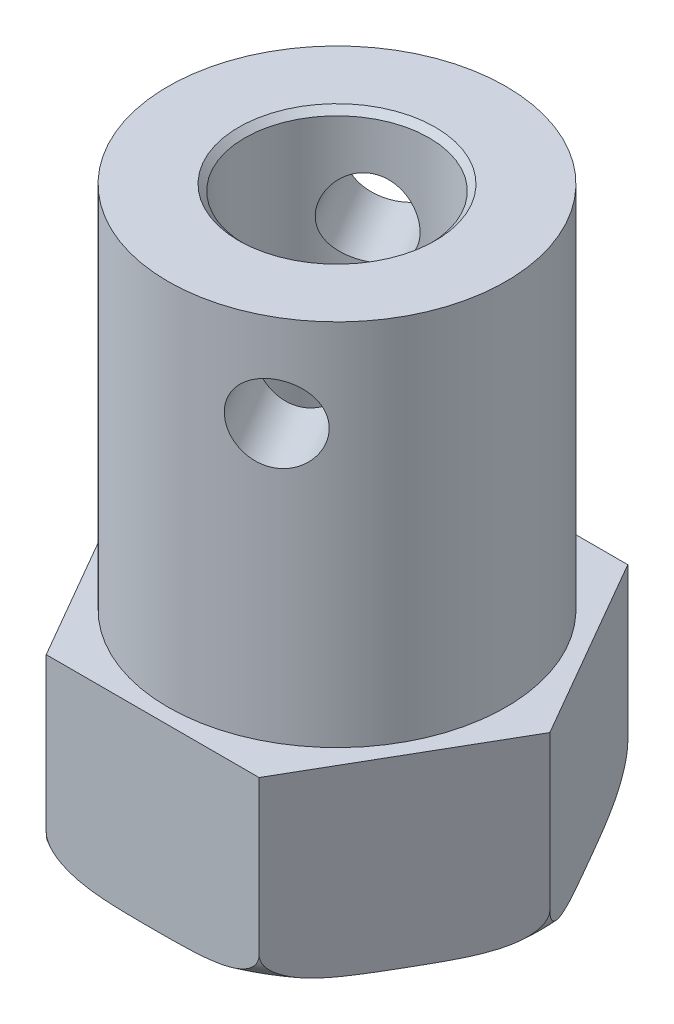
SolidWorks part; units mm, degrees
material "Acero inoxidable al cromo"
ref_plane "Front Plane" through (0, 0, 0) normal (0, 0, 1) x (1, 0, 0)
ref_plane "Top Plane" through (0, 0, 0) normal (0, 1, 0) x (1, 0, 0)
ref_plane "Right Plane" through (0, 0, 0) normal (1, 0, 0) x (0, 0, -1)
sketch "Sketch1" plane through (0, 0, 0) normal (0, 1, 0) x (1, 0, 0)
  line L1 (3.4641, -6) -> (6.9282, 0)
  line L2 (6.9282, 0) -> (3.4641, 6)
  line L3 (3.4641, 6) -> (-3.4641, 6)
  line L4 (-3.4641, 6) -> (-6.9282, 0)
  line L5 (-6.9282, 0) -> (-3.4641, -6)
  line L6 (-3.4641, -6) -> (3.4641, -6)
  circle A0 centre (0, 0) radius 6 construction
  dimension "D1" = 12
extrude "BASE" add sketch "Sketch1" along normal blind 6
sketch "Sketch2" plane through (0, 6, 0) normal (0, 1, 0) x (1, 0, 0)
  line L1 (0, 5.5) -> (0, 6) construction
  line L2 (3.4641, 6) -> (-3.4641, 6) construction
  circle A0 centre (0, 0) radius 5.5
  dimension "D1" = 0.5
  dimension "D2" = 11
extrude "SHAFT HOLDING BODY" add sketch "Sketch2" along normal blind 12
hole_wizard "M4x0.7 Tapped Hole1" positions "Sketch3" profile "Sketch4" tap size "M4x0.7" standard "ANSI Metric" end condition through all
sketch "Sketch3" plane through (0, 0, 0) normal (0, -1, 0) x (-1, 0, 0)
  point P0 (0, 0)
sketch "Sketch4" plane through (0, 0, 0) normal (1, 0, 0) x (0, 0, -1)
  line L0 (0, 0) -> (0, 18)
  line L1 (0, 18) -> (1.65, 18)
  line L2 (1.65, 18) -> (1.65, 0.35)
  line L3 (1.65, 0.35) -> (2, 0)
  line L5 (2, 0) -> (0, 0)
  line L6 (-1.65, 0.35) -> (-2, 0) construction
  line L11 (0, -6.35) -> (0, 107.95) construction
  dimension "Thru Tap Drill Dia." = 3.3
  dimension "Thru Tap Drill Depth" = 18
  dimension "Near C'Sink Dia." = 4
  dimension "Near C'Sink Angle" = 90
cosmetic thread "Hole Thread3" parameters "D2"=4
ref_plane "SET SCREW REFERENCE PLANE" through (2.75, 6, 4.7631) normal (0.5, 0, 0.866) x (0.866, 0, -0.5)
hole_wizard "M3x0.5 Tapped Hole1" positions "Sketch7" profile "Sketch8" tap size "M3x0.5" standard "ANSI Metric" end condition through all
sketch "Sketch7" plane through (2.75, 6, 4.7631) normal (0.5, 0, 0.866) x (0.866, 0, -0.5)
  line L0 (5.5, 12) -> (-5.5, 12) construction
  line L1 (0, 12) -> (0, 0) construction
  line L2 (0, 12) -> (0, 9) construction
  point P0 (0, 9)
  dimension "D1" = 3
sketch "Sketch8" plane through (2.75, 15, 4.7631) normal (0, 1, 0) x (0.866, 0, -0.5)
  line L0 (0, 0) -> (0, 14.1603)
  line L1 (0, 14.1603) -> (1.25, 14.1603)
  line L2 (1.25, 14.1603) -> (1.25, 0)
  line L5 (1.25, 0) -> (0, 0)
  line L11 (0, -6.35) -> (0, 107.95) construction
  dimension "Thru Tap Drill Dia." = 2.5
  dimension "Thru Tap Drill Depth" = 14.1603
cosmetic thread "Hole Thread2" parameters "D2"=3
sketch "Sketch9" plane through (0, 0, 0) normal (0, 0, 1) x (1, 0, 0)
  line L0 (-6.9282, 1) -> (-6.9282, 0)
  line L1 (-6.9282, 0) -> (-5.9282, 0)
  line L2 (6, 0) -> (-6, 0) construction
  line L4 (-6.9282, 6) -> (-6.9282, 0) construction
  arc A0 (-6.9282, 1) -> (-5.9282, 0) centre (-5.9282, 1) ccw
  dimension "D1" = 1
revolve "BASE CHAMFER RELIEF" cut sketch "Sketch9" angle 360 about axis through (0, 0, 0) along (0, 1, 0)
sketch "Sketch13" plane through (0, 18, 0) normal (0, 1, 0) x (1, 0, 0)
  circle A0 centre (0, 0) radius 3
  dimension "D1" = 6
extrude "SHAFT HOLE" cut sketch "Sketch13" against normal offset from surface (13.5 mm away) 4.5 up to face at (0, 0, -2)
chamfer "SH C" distance 0.2 angle 45 1 edges at (0, 18, 3)
